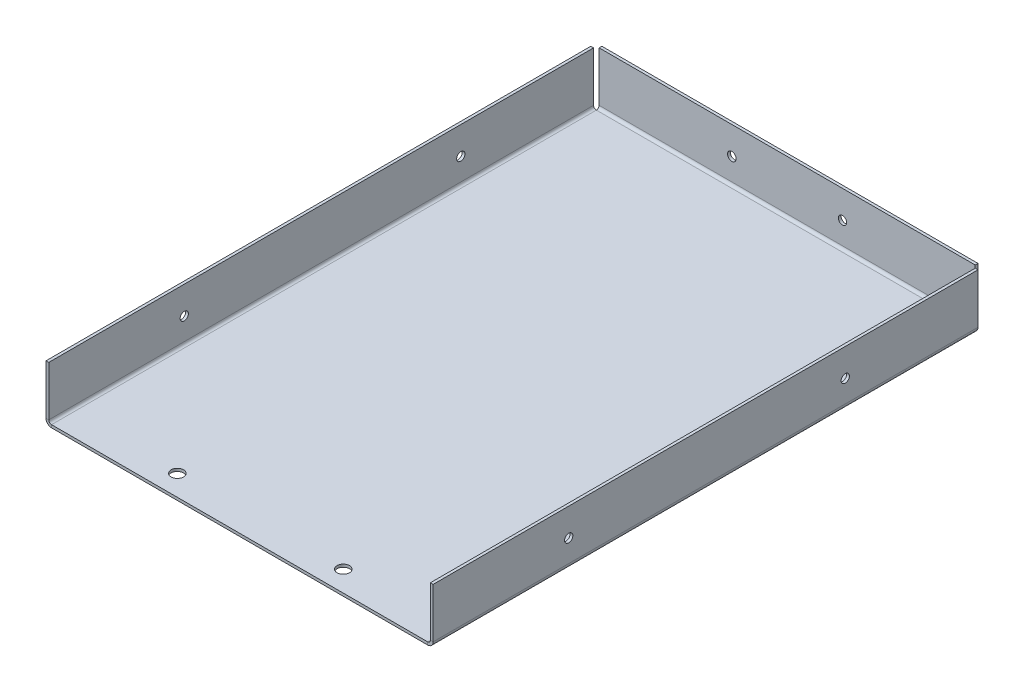
SolidWorks part; units mm, degrees
note: The reader was unsure of these and kept them because the rebuilt part matched: flange length of "Edge-Flange1", "Edge-Flange2", "Edge-Flange3".
material "AISI 1020"
ref_plane "Front Plane" through (0, 0, 0) normal (0, 0, 1) x (1, 0, 0)
ref_plane "Top Plane" through (0, 0, 0) normal (0, 1, 0) x (1, 0, 0)
ref_plane "Right Plane" through (0, 0, 0) normal (1, 0, 0) x (0, 0, -1)
sketch "Sketch1" plane through (0, 0, 0) normal (0, 1, 0) x (1, 0, 0)
  line L1 (0, 0) -> (136, 0)
  line L2 (0, 0) -> (0, 198)
  line L3 (0, 198) -> (136, 198)
  line L4 (136, 0) -> (136, 198)
  dimension "D1" = 136
  dimension "D2" = 198
base flange "Base-Flange1" sketch "Sketch1" thickness 1 reverse thickness direction no parameters "D1"=1
edge flange "Edge-Flange1" sketch "Sketch8" flange angle 90 flange length 20 flange position material outside bend radius 1 thickness 1 relief rectangular parameters "D6"=10
sketch "Sketch8" plane through (0, 0, -198) normal (0, 0, -1) x (-1, 0, 0)
  line L2 (-136, 0) -> (-136, 19)
  line L3 (-136, 19) -> (0, 19)
  line L4 (0, 19) -> (0, 0)
  line L7 (-136, 0) -> (0, 0) construction
  line L8 (-136, 0) -> (0, 0)
bend "EdgeBend1" bend radius 1 bend angle 90 parameters "D5"=1
edge flange "Edge-Flange2" sketch "Sketch11" flange angle 90 flange length 20 flange position bend outside bend radius 1 thickness 1 relief rectangular parameters "D6"=10
sketch "Sketch11" plane through (136, 0, 0) normal (1, 0, 0) x (0, 0, -1)
  line L0 (0, 0) -> (197, 0) construction
  line L1 (0, 0) -> (197, 0)
  line L2 (0, 0) -> (0, 19)
  line L3 (0, 19) -> (197, 19)
  line L4 (197, 19) -> (197, 0)
bend "EdgeBend2" bend radius 1 bend angle 90 parameters "D5"=2
edge flange "Edge-Flange3" sketch "Sketch14" flange angle 90 flange length 20 flange position bend outside bend radius 1 thickness 1 relief rectangular parameters "D6"=10
sketch "Sketch14" plane through (0, 0, 0) normal (-1, 0, 0) x (0, 0, 1)
  line L0 (-197, 0) -> (0, 0) construction
  line L1 (-197, 0) -> (0, 0)
  line L2 (-197, 0) -> (-197, 19)
  line L3 (-197, 19) -> (0, 19)
  line L4 (0, 19) -> (0, 0)
bend "EdgeBend3" bend radius 1 bend angle 90 parameters "D5"=3
extrude "Cut-Extrude1" cut sketch "Sketch18" along normal through all and the other way blind 159
sketch "Sketch18" plane through (-3, 352.0517, -347.4) normal (-1, 0, 0) x (0, 0, -1)
  line L0 (-340.3963, 343.0517) -> (-194.3431, 343.0517) construction
  line L3 (-321.827, 103.0517) -> (-152.9574, 103.0517) construction
  circle A0 centre (-298.4, 343.0517) radius 1.5
  circle A1 centre (-198.4, 343.0517) radius 1.5
  circle A2 centre (-298.4, 103.0517) radius 1.5
  circle A3 centre (-198.4, 103.0517) radius 1.5
extrude "Cut-Extrude2" cut sketch "Sketch21" against normal blind 278
sketch "Sketch21" plane through (-57.0625, -1, -347.4) normal (0, -1, 0) x (0, 0, 1)
  line L0 (339.9, -73.287) -> (339.9, -197.4958) construction
  circle A0 centre (339.9, -95.0625) radius 2.25
  circle A1 centre (339.9, -155.0625) radius 2.25
extrude "Cut-Extrude7" cut sketch "Sketch26" against normal blind 10
sketch "Sketch26" plane through (-57.0625, 352.0517, -200) normal (0, 0, -1) x (1, 0, 0)
  line L0 (68.6525, 103.0517) -> (169.9595, 103.0517) construction
  line L1 (96.7868, 343.0517) -> (198.0938, 343.0517) construction
  circle A0 centre (105.0625, 343.0517) radius 1.5
  circle A1 centre (145.0625, 343.0517) radius 1.5
  circle A2 centre (105.0625, 103.0517) radius 1.5
  circle A3 centre (145.0625, 103.0517) radius 1.55
extrude "Cut-Extrude14" cut sketch "Sketch33" against normal blind 10
sketch "Sketch33" plane through (193.0625, -94.0517, -200) normal (0, 0, -1) x (-1, 0, 0)
  line L0 (68.6525, 103.0517) -> (169.9595, 103.0517) construction
  line L1 (96.7868, 343.0517) -> (198.0938, 343.0517) construction
  circle A0 centre (105.0625, 343.0517) radius 1.5
  circle A1 centre (145.0625, 343.0517) radius 1.5
  circle A2 centre (105.0625, 103.0517) radius 1.5
  circle A3 centre (145.0625, 103.0517) radius 1.55
sketch "Bend-Lines1" [suppressed] plane through (0, 0, 0) normal (0, 1, 0) x (1, 0, 0)
sketch "Bounding-Box1" [suppressed] plane through (0, 0, 0) normal (0, 1, 0) x (1, 0, 0)
sheet metal parameters "Sheet-Metal1" thickness 1 parameters "D1"=1
flat pattern "Flat-Pattern1" [suppressed]
sketch "Bend-Lines2" plane through (0, 0, 0) normal (0, 1, 0) x (1, 0, 0)
sketch3d "Bounding-Box2" [suppressed]
  line L0 (0, 0, 0) -> (0, 200, 0) construction
  line L1 (-138, 0, 0) -> (-138, 200, 0) construction
  line L2 (0, 0, 0) -> (-138, 0, 0) construction
  line L3 (0, 200, 0) -> (-138, 200, 0) construction
sheet metal parameters "Sheet-Metal2" thickness 1 parameters "D1"=1
flat pattern "Flat-Pattern1"
sketch "Bend-Lines2" plane through (0, 0, 0) normal (0, 1, 0) x (1, 0, 0)
  line L0 (138, 200.1781) -> (0, 200.1781) construction
  line L1 (138, 200.1781) -> (0, 200.1781) construction
sketch3d "Bounding-Box2" [suppressed]
  line L0 (0, 0, 0) -> (0, 219.3562, 0) construction
  line L1 (138, 0, 0) -> (138, 219.3562, 0) construction
  line L2 (0, 0, 0) -> (138, 0, 0) construction
  line L3 (0, 219.3562, 0) -> (138, 219.3562, 0) construction
bend of the flat pattern "Flatten-<EdgeBend1>1"
sheet metal parameters "Sheet-Metal3" thickness 1 parameters "D1"=1
flat pattern "Flat-Pattern1"
sketch "Bend-Lines2" plane through (0, 0, 0) normal (0, 1, 0) x (1, 0, 0)
  line L0 (138, 200.1781) -> (0, 200.1781) construction
  line L1 (138, 200.1781) -> (0, 200.1781) construction
  line L2 (138.1781, 0) -> (138.1781, 199) construction
  line L3 (138.1781, 0) -> (138.1781, 199) construction
sketch3d "Bounding-Box2" [suppressed]
  line L0 (0, 0, 0) -> (0, 219.3562, 0) construction
  line L1 (157.3562, 0, 0) -> (157.3562, 219.3562, 0) construction
  line L2 (0, 0, 0) -> (157.3562, 0, 0) construction
  line L3 (0, 219.3562, 0) -> (157.3562, 219.3562, 0) construction
bend of the flat pattern "Flatten-<EdgeBend1>1"
bend of the flat pattern "Flatten-<EdgeBend2>1"
sheet metal parameters "Sheet-Metal4" thickness 1 parameters "D1"=1
flat pattern "Flat-Pattern1"
sketch "Bend-Lines2" plane through (0, 0, 0) normal (0, 1, 0) x (1, 0, 0)
  line L0 (136, 198.1781) -> (0, 198.1781) construction
  line L1 (136, 198.1781) -> (0, 198.1781) construction
  line L2 (137.1781, 0) -> (137.1781, 197) construction
  line L3 (137.1781, 0) -> (137.1781, 197) construction
  line L4 (-1.1781, 197) -> (-1.1781, 0) construction
  line L5 (-1.1781, 197) -> (-1.1781, 0) construction
sketch3d "Bounding-Box2" [suppressed]
  line L0 (-20.3562, 0, 0) -> (-20.3562, 217.3562, 0) construction
  line L1 (156.3562, 0, 0) -> (156.3562, 217.3562, 0) construction
  line L2 (-20.3562, 0, 0) -> (156.3562, 0, 0) construction
  line L3 (-20.3562, 217.3562, 0) -> (156.3562, 217.3562, 0) construction
bend of the flat pattern "Flatten-<EdgeBend1>1"
bend of the flat pattern "Flatten-<EdgeBend2>1"
bend of the flat pattern "Flatten-<EdgeBend3>1"
sheet metal parameters "Sheet-Metal6" thickness 1 parameters "D1"=1
flat pattern "Flat-Pattern1"
sketch "Bend-Lines2" plane through (0, 0, 0) normal (0, 1, 0) x (1, 0, 0)
  line L0 (136, 198.1781) -> (0, 198.1781) construction
  line L1 (136, 198.1781) -> (0, 198.1781) construction
  line L2 (137.1781, 0) -> (137.1781, 197) construction
  line L3 (137.1781, 0) -> (137.1781, 197) construction
  line L4 (-1.1781, 197) -> (-1.1781, 0) construction
  line L5 (-1.1781, 197) -> (-1.1781, 0) construction
sketch3d "Bounding-Box2" [suppressed]
  line L0 (-20.3562, 0, 0) -> (-20.3562, 217.3562, 0) construction
  line L1 (156.3562, 0, 0) -> (156.3562, 217.3562, 0) construction
  line L2 (-20.3562, 0, 0) -> (156.3562, 0, 0) construction
  line L3 (-20.3562, 217.3562, 0) -> (156.3562, 217.3562, 0) construction
bend of the flat pattern "Flatten-<EdgeBend1>1"
bend of the flat pattern "Flatten-<EdgeBend2>1"
bend of the flat pattern "Flatten-<EdgeBend3>1"
sheet metal parameters "Sheet-Metal8" thickness 1 parameters "D1"=1
flat pattern "Flat-Pattern1"
sketch "Bend-Lines2" plane through (0, 0, 0) normal (0, 1, 0) x (1, 0, 0)
  line L0 (136, 198.1781) -> (0, 198.1781) construction
  line L1 (136, 198.1781) -> (0, 198.1781) construction
  line L2 (137.1781, 0) -> (137.1781, 197) construction
  line L3 (137.1781, 0) -> (137.1781, 197) construction
  line L4 (-1.1781, 197) -> (-1.1781, 0) construction
  line L5 (-1.1781, 197) -> (-1.1781, 0) construction
sketch3d "Bounding-Box2" [suppressed]
  line L0 (-20.3562, 0, 0) -> (-20.3562, 217.3562, 0) construction
  line L1 (156.3562, 0, 0) -> (156.3562, 217.3562, 0) construction
  line L2 (-20.3562, 0, 0) -> (156.3562, 0, 0) construction
  line L3 (-20.3562, 217.3562, 0) -> (156.3562, 217.3562, 0) construction
bend of the flat pattern "Flatten-<EdgeBend1>1"
bend of the flat pattern "Flatten-<EdgeBend2>1"
bend of the flat pattern "Flatten-<EdgeBend3>1"
sheet metal parameters "Sheet-Metal9" thickness 1 parameters "D1"=1
flat pattern "Flat-Pattern1"
sketch "Bend-Lines2" plane through (0, 0, 0) normal (0, 1, 0) x (1, 0, 0)
  line L0 (136, 198.1781) -> (0, 198.1781) construction
  line L1 (136, 198.1781) -> (0, 198.1781) construction
  line L2 (137.1781, 0) -> (137.1781, 197) construction
  line L3 (137.1781, 0) -> (137.1781, 197) construction
  line L4 (-1.1781, 197) -> (-1.1781, 0) construction
  line L5 (-1.1781, 197) -> (-1.1781, 0) construction
sketch3d "Bounding-Box2" [suppressed]
  line L0 (-20.3562, 0, 0) -> (-20.3562, 217.3562, 0) construction
  line L1 (156.3562, 0, 0) -> (156.3562, 217.3562, 0) construction
  line L2 (-20.3562, 0, 0) -> (156.3562, 0, 0) construction
  line L3 (-20.3562, 217.3562, 0) -> (156.3562, 217.3562, 0) construction
bend of the flat pattern "Flatten-<EdgeBend1>1"
bend of the flat pattern "Flatten-<EdgeBend2>1"
bend of the flat pattern "Flatten-<EdgeBend3>1"
sheet metal parameters "Sheet-Metal10" thickness 1 parameters "D1"=1
flat pattern "Flat-Pattern1"
sketch "Bend-Lines2" plane through (0, 0, 0) normal (0, 1, 0) x (1, 0, 0)
  line L0 (136, 198.1781) -> (0, 198.1781) construction
  line L1 (136, 198.1781) -> (0, 198.1781) construction
  line L2 (137.1781, 0) -> (137.1781, 197) construction
  line L3 (137.1781, 0) -> (137.1781, 197) construction
  line L4 (-1.1781, 197) -> (-1.1781, 0) construction
  line L5 (-1.1781, 197) -> (-1.1781, 0) construction
sketch3d "Bounding-Box2" [suppressed]
  line L0 (-20.3562, 0, 0) -> (-20.3562, 217.3562, 0) construction
  line L1 (156.3562, 0, 0) -> (156.3562, 217.3562, 0) construction
  line L2 (-20.3562, 0, 0) -> (156.3562, 0, 0) construction
  line L3 (-20.3562, 217.3562, 0) -> (156.3562, 217.3562, 0) construction
bend of the flat pattern "Flatten-<EdgeBend1>1"
bend of the flat pattern "Flatten-<EdgeBend2>1"
bend of the flat pattern "Flatten-<EdgeBend3>1"
